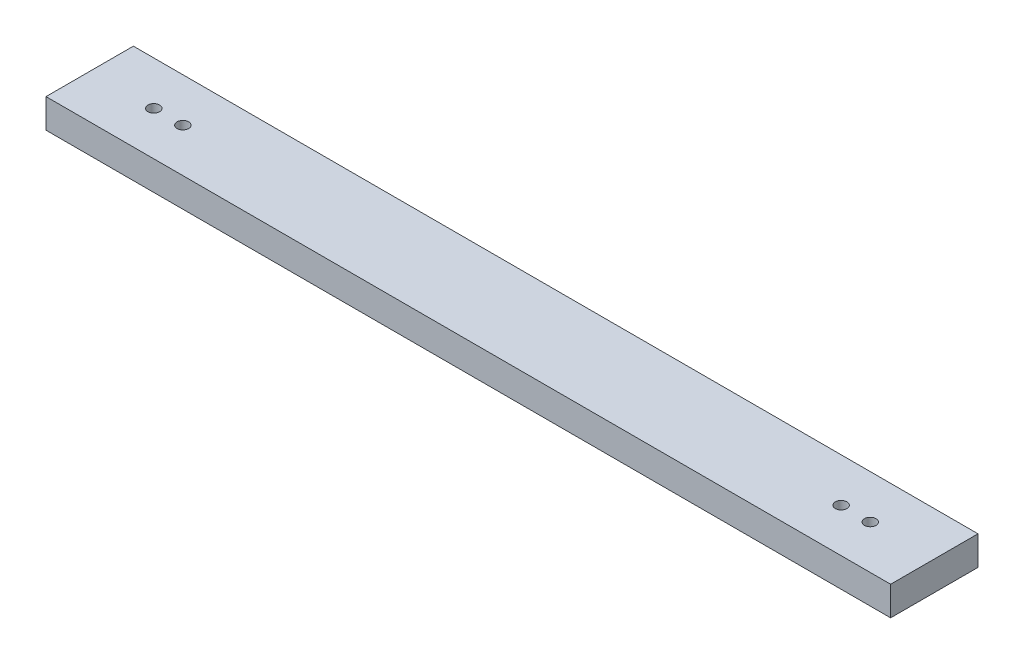
SolidWorks part; units mm, degrees
ref_plane "Front Plane" through (0, 0, 0) normal (0, 0, 1) x (1, 0, 0)
ref_plane "Top Plane" through (0, 0, 0) normal (0, 1, 0) x (1, 0, 0)
ref_plane "Right Plane" through (0, 0, 0) normal (1, 0, 0) x (0, 0, -1)
sketch "Sketch3" plane through (0, 0, 0) normal (0, 1, 0) x (1, 0, 0)
  line L1 (0, 80) -> (580, 80)
  line L2 (0, 80) -> (0, 20)
  line L3 (0, 20) -> (580, 20)
  line L4 (580, 80) -> (580, 20)
  dimension "D1" = 580
  dimension "D2" = 60
extrude "Boss-Extrude1" add sketch "Sketch3" along normal blind 20
sketch "Sketch4" plane through (0, 20, 0) normal (0, 1, 0) x (1, 0, 0)
  circle A0 centre (44, 50) radius 4
  circle A1 centre (64, 50) radius 4
  circle A2 centre (516, 50) radius 4
  circle A3 centre (536, 50) radius 4
  dimension "D3" = 8
  dimension "D4" = 8
  dimension "D2" = 20
extrude "Cut-Extrude1" cut sketch "Sketch4" against normal through all
